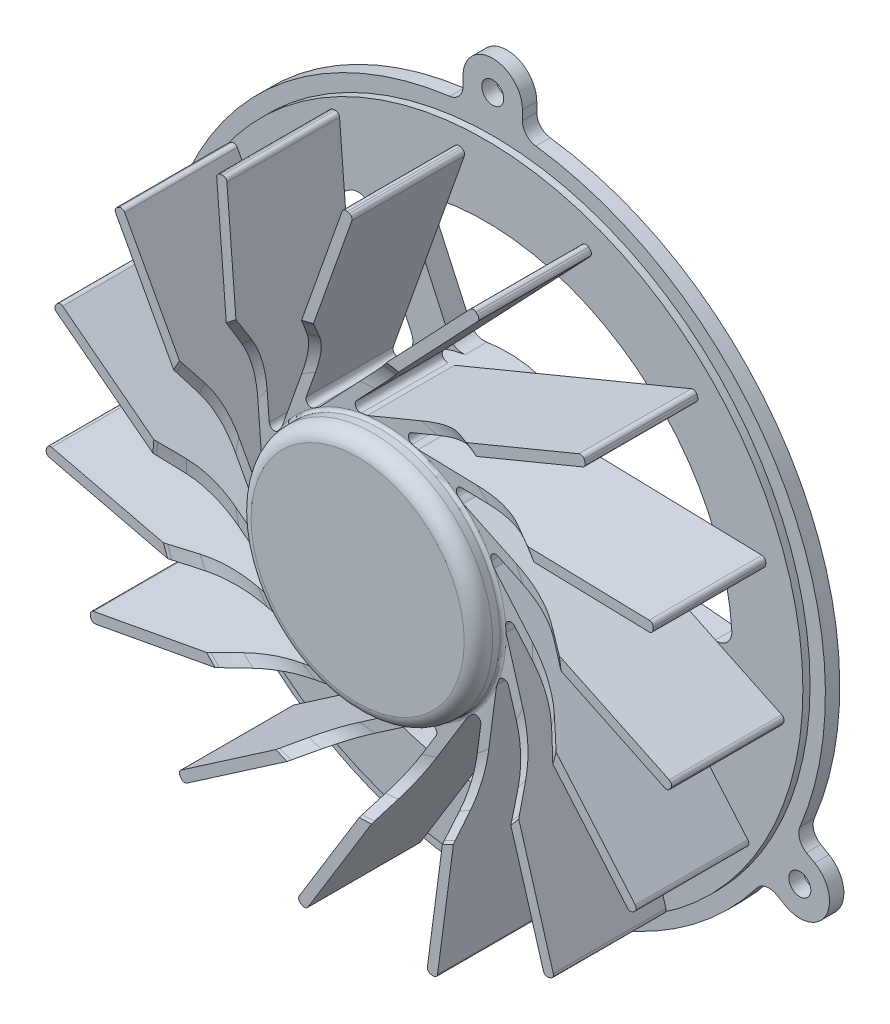
SolidWorks part; units mm, degrees
ref_plane "Front Plane" through (0, 0, 0) normal (0, 0, 1) x (1, 0, 0)
ref_plane "Top Plane" through (0, 0, 0) normal (0, 1, 0) x (1, 0, 0)
ref_plane "Right Plane" through (0, 0, 0) normal (1, 0, 0) x (0, 0, -1)
sketch "Sketch1" plane through (0, 0, 0) normal (0, 0, 1) x (1, 0, 0)
  line L0 (-2.9, 34.641) -> (2.9, 34.641) construction
  line L1 (0, 37.541) -> (0, -32.5) construction
  line L2 (-2.9, 34.641) -> (-2.9, 33.7141)
  line L3 (2.9, 34.641) -> (2.9, 33.7141)
  line L4 (28.55, -19.832) -> (27.7473, -19.3685)
  line L5 (31.45, -14.809) -> (30.6473, -14.3456)
  line L6 (-31.45, -14.809) -> (-30.6473, -14.3456)
  line L7 (-28.55, -19.832) -> (-27.7473, -19.3685)
  line L8 (0, 0) -> (2.9, 32.3704) construction
  line L9 (0, 0) -> (26.5836, -18.6967) construction
  line L10 (0, 0) -> (-29.4836, -13.6737) construction
  line L11 (0, 0) -> (-4.9858, 10.9152) construction
  line L12 (22.4164, -0.1297) -> (13.1694, 0.7526)
  line L13 (-11.0959, 19.478) -> (-7.2365, 11.0288)
  line L14 (12.7895, -3.2293) -> (22.0364, -4.1116)
  line L15 (-3.5981, 12.6907) -> (-7.4575, 21.1399)
  line L17 (-11.3205, -19.3483) -> (-5.933, -11.7813)
  line L18 (-9.1914, -9.4614) -> (-14.579, -17.0283)
  line L19 (0, 0) -> (-6.9599, -9.7754) construction
  line L20 (0, 0) -> (23.991, -2.289) construction
  arc A0 (-4.2059, 32.2267) -> (-30.0121, -12.471) centre (0, 0) ccw
  circle A1 centre (0, 34.641) radius 1.075
  arc A2 (2.9, 34.641) -> (-2.9, 34.641) centre (0, 34.641) ccw
  arc A3 (28.55, -19.832) -> (31.45, -14.809) centre (30, -17.3205) ccw
  circle A4 centre (30, -17.3205) radius 1.075
  arc A5 (-31.45, -14.809) -> (-28.55, -19.832) centre (-30, -17.3205) ccw
  circle A6 centre (-30, -17.3205) radius 1.075
  arc A7 (-25.8062, -19.7558) -> (25.8062, -19.7558) centre (0, 0) ccw
  arc A8 (30.0121, -12.471) -> (4.2059, 32.2267) centre (0, 0) ccw
  arc A9 (-27.7473, -19.3685) -> (-25.8062, -19.7558) centre (-26.9973, -20.6676) cw
  arc A10 (-30.6473, -14.3456) -> (-30.0121, -12.471) centre (-31.3973, -13.0465) ccw
  arc A11 (27.7473, -19.3685) -> (25.8062, -19.7558) centre (26.9973, -20.6676) ccw
  arc A12 (30.6473, -14.3456) -> (30.0121, -12.471) centre (31.3973, -13.0465) cw
  arc A13 (2.9, 33.7141) -> (4.2059, 32.2267) centre (4.4, 33.7141) ccw
  arc A14 (-2.9, 33.7141) -> (-4.2059, 32.2267) centre (-4.4, 33.7141) cw
  arc A15 (-13.2873, 20.1062) -> (-16.8496, -17.2308) centre (0, 0) ccw
  arc A16 (11.8328, 1.9963) -> (-1.9855, 11.8346) centre (0, 0) ccw
  arc A17 (24.0561, 1.454) -> (-6.4975, 23.2076) centre (0, 0) ccw
  arc A18 (-10.7688, -21.5602) -> (23.3471, -5.9768) centre (0, 0) ccw
  arc A19 (-4.1876, -11.2456) -> (11.2418, -4.1978) centre (0, 0) ccw
  arc A20 (-7.6452, 9.2494) -> (-9.2563, -7.6368) centre (0, 0) ccw
  arc A21 (-11.3205, -19.3483) -> (-10.7688, -21.5602) centre (-10.0986, -20.2183) ccw
  arc A22 (-14.579, -17.0283) -> (-16.8496, -17.2308) centre (-15.8009, -16.1583) cw
  arc A23 (-9.1914, -9.4614) -> (-9.2563, -7.6368) centre (-10.4134, -8.5914) ccw
  arc A24 (-5.933, -11.7813) -> (-4.1876, -11.2456) centre (-4.711, -12.6513) cw
  arc A25 (12.7895, -3.2293) -> (11.2418, -4.1978) centre (12.647, -4.7226) ccw
  arc A26 (22.0364, -4.1116) -> (23.3471, -5.9768) centre (21.894, -5.6048) cw
  arc A27 (13.1694, 0.7526) -> (11.8328, 1.9963) centre (13.3119, 2.2458) cw
  arc A28 (-11.0959, 19.478) -> (-13.2873, 20.1062) centre (-12.4603, 18.8548) ccw
  arc A29 (-6.4975, 23.2076) -> (-7.4575, 21.1399) centre (-6.0931, 21.7631) ccw
  arc A30 (-3.5981, 12.6907) -> (-1.9855, 11.8346) centre (-2.2337, 13.3139) ccw
  arc A31 (-7.2365, 11.0288) -> (-7.6452, 9.2494) centre (-8.6009, 10.4055) cw
  arc A32 (24.0561, 1.454) -> (22.4164, -0.1297) centre (22.5588, 1.3635) cw
  circle A33 centre (0, 0) radius 31
  point P32 (26.5836, -18.6967)
  point P37 (2.9, 32.3704)
  point P60 (0, 0)
  point P78 (-6.7353, 9.9316)
  dimension "D1" = 65
  dimension "D2" = 2.15
  dimension "D3" = 5.8
  dimension "D6" = 1.5
  dimension "D7" = 8.4
  dimension "D8" = 24
  dimension "D12" = 1.5
  dimension "D13" = 1.5
  dimension "D14" = 62
  dimension "D5" = 120
  dimension "D9" = 2
  dimension "D10" = 2
  dimension "D15" = 60
  dimension "D4" = 3
  dimension "D11" = 3
extrude "extrude-bottom" add sketch "Sketch1" along normal blind 1.4 contours A33 A17 A32 L12 A27 A16 A30 L15 A29 L14 A26 A18 A21 L17 A24 A19 A25 L13 A31 A20 A23 L18 A22 A15 A28 | L2 A14 A0 A10 L6 A5 L7 A9 A7 A11 L4 A3 L5 A12 A8 A13 L3 A2 A33 A6 A4 A1 region at (0, 36.58, 0) region at (0, 0, 0)
extrude "extrude-offset" add sketch "Sketch1<3>" along normal blind 2.1 contours A33 A17 A32 L12 A27 A16 A30 L15 A29 L14 A26 A18 A21 L17 A24 A19 A25 L13 A31 A20 A23 L18 A22 A15 A28 region at (0, 0, 0)
sketch "Sketch1<3>" plane through (0, 0, 0) normal (0, 0, 1) x (1, 0, 0) same geometry as "Sketch1"
sketch "Sketch2" plane through (0, 0, 2.1) normal (0, 0, 1) x (1, 0, 0)
  circle A0 centre (0, 0) radius 12
extrude "extrude-fan-base" add sketch "Sketch2" along normal blind 1.5
sketch "Sketch3" plane through (0, 0, 3.6) normal (0, 0, 1) x (1, 0, 0)
  line L0 (0, 41.7552) -> (0, -41.8706) construction
  line L1 (56.9418, 0) -> (-60.0855, 0) construction
  line L2 (0, 12) -> (63.232, 12) construction
  line L3 (63.232, 12) -> (-76.4509, 12) construction
  line L4 (0, 12) -> (22.1731, 21.1844) construction
  line L5 (21.6122, 21.4933) -> (-1.5489, 11.8996)
  line L6 (2.7699, 12.6061) -> (21.9949, 20.5694)
  line L7 (22.1348, 21.2768) -> (22.2114, 21.092)
  line L8 (28.4858, 10.8446) -> (3.425, 11.5008)
  line L9 (7.6578, 10.3897) -> (28.4597, 9.8449)
  line L10 (28.8752, 10.4343) -> (28.87, 10.2343)
  line L11 (4.8808, 10.9625) -> (28.8726, 10.3343) construction
  line L12 (30.434, -1.6792) -> (7.8067, 9.1135)
  line L13 (11.2216, 6.3767) -> (30.0035, -2.5818)
  line L14 (30.6228, -2.2124) -> (30.5367, -2.393)
  line L15 (8.9177, 8.0296) -> (30.5798, -2.3027) construction
  line L16 (27.1199, -13.9127) -> (10.8386, 5.1503)
  line L17 (12.8451, 1.2612) -> (26.3594, -14.5621)
  line L18 (27.0755, -14.4766) -> (26.9234, -14.6065)
  line L19 (11.4127, 3.7082) -> (26.9994, -14.5415) construction
  line L20 (19.1164, -23.7405) -> (11.9963, 0.2966)
  line L21 (12.2475, -4.0724) -> (18.1576, -24.0245)
  line L22 (18.8465, -24.2376) -> (18.6547, -24.2944)
  line L23 (11.9343, -1.2543) -> (18.7506, -24.266) construction
  line L24 (7.8076, -29.4634) -> (11.0798, -4.6084)
  line L25 (9.5323, -8.7018) -> (6.8162, -29.3328)
  line L26 (7.3588, -29.8077) -> (7.1605, -29.7816)
  line L27 (10.3923, -6) -> (7.2597, -29.7947) construction
  line L28 (-4.8512, -30.0918) -> (8.2475, -8.7166)
  line L29 (5.1688, -11.8267) -> (-5.7039, -29.5693)
  line L30 (-5.4013, -30.2238) -> (-5.5718, -30.1193)
  line L31 (7.0534, -9.7082) -> (-5.4865, -30.1716) construction
  line L32 (-16.6712, -25.517) -> (3.9891, -11.3175)
  line L33 (-0.0884, -12.9065) -> (-17.2376, -24.6929)
  line L34 (-17.2274, -25.4139) -> (-17.3407, -25.2491)
  line L35 (2.4949, -11.7378) -> (-17.2841, -25.3315) construction
  line L36 (-25.6086, -16.5302) -> (-0.959, -11.9616)
  line L37 (-5.3303, -11.7548) -> (-25.7909, -15.5469)
  line L38 (-26.0748, -16.2097) -> (-26.1113, -16.0131)
  line L39 (-2.4949, -11.7378) -> (-26.0931, -16.1114) construction
  line L40 (-30.1181, -4.6851) -> (-5.7413, -10.5374)
  line L41 (-9.6506, -8.5705) -> (-29.8846, -3.7127)
  line L42 (-30.4136, -4.2028) -> (-30.367, -4.0083)
  line L43 (-7.0534, -9.7082) -> (-30.3903, -4.1055) construction
  line L44 (-29.4198, 7.9701) -> (-9.5309, -7.2912)
  line L45 (-12.3022, -3.9043) -> (-28.8111, 8.7634)
  line L46 (-29.4937, 8.5309) -> (-29.3719, 8.6896)
  line L47 (-10.3923, -6) -> (-29.4328, 8.6103) construction
  line L48 (-23.6346, 19.2472) -> (-11.6725, -2.7843)
  line L49 (-12.8266, 1.437) -> (-22.7558, 19.7243)
  line L50 (-23.474, 19.7896) -> (-23.2982, 19.885)
  line L51 (-11.9343, -1.2543) -> (-23.3861, 19.8373) construction
  line L52 (-13.7628, 27.1962) -> (-11.7958, 2.2041)
  line L53 (-11.1332, 6.5298) -> (-12.7659, 27.2747)
  line L54 (-13.3954, 27.6264) -> (-13.196, 27.6421)
  line L55 (-11.4127, 3.7082) -> (-13.2957, 27.6342) construction
  line L56 (-1.5112, 30.4428) -> (-9.8796, 6.8113)
  line L57 (-7.5148, 10.4936) -> (-0.5686, 30.109)
  line L58 (-1.0006, 30.6863) -> (-0.8121, 30.6196)
  line L59 (-8.9177, 8.0296) -> (-0.9064, 30.653) construction
  line L60 (11.0016, 28.4256) -> (-6.255, 10.2408)
  line L61 (-2.597, 12.6429) -> (11.727, 27.7372)
  line L62 (11.5671, 28.4404) -> (11.7122, 28.3027)
  line L63 (-4.8808, 10.9625) -> (11.6397, 28.3715) construction
  circle A0 centre (0, 0) radius 30 construction
  arc A1 (-1.5489, 11.8996) -> (-2.1449, 11.8068) centre (0, 0) ccw
  circle A2 centre (0, 0) radius 12 construction
  arc A3 (21.9949, 20.5694) -> (22.2114, 21.092) centre (21.8418, 20.9389) ccw
  arc A4 (21.6122, 21.4933) -> (22.1348, 21.2768) centre (21.7653, 21.1237) cw
  arc A5 (2.7699, 12.6061) -> (2.8428, 11.6584) centre (2.9612, 12.1442) ccw
  arc A6 (7.6578, 10.3897) -> (7.3389, 9.4942) centre (7.6447, 9.8898) ccw
  arc A7 (28.4858, 10.8446) -> (28.8752, 10.4343) centre (28.4754, 10.4447) cw
  arc A8 (28.4597, 9.8449) -> (28.87, 10.2343) centre (28.4701, 10.2448) ccw
  arc A9 (11.2216, 6.3767) -> (10.5661, 5.6884) centre (11.0063, 5.9254) ccw
  arc A10 (30.434, -1.6792) -> (30.6228, -2.2124) centre (30.2618, -2.0402) cw
  arc A11 (30.0035, -2.5818) -> (30.5367, -2.393) centre (30.1757, -2.2208) ccw
  arc A12 (12.8451, 1.2612) -> (11.9663, 0.899) centre (12.4649, 0.9365) ccw
  arc A13 (27.1199, -13.9127) -> (27.0755, -14.4766) centre (26.8157, -14.1724) cw
  arc A14 (26.3594, -14.5621) -> (26.9234, -14.6065) centre (26.6636, -14.3023) ccw
  arc A15 (12.2475, -4.0724) -> (11.2974, -4.0458) centre (11.7681, -4.2144) ccw
  arc A16 (19.1164, -23.7405) -> (18.8465, -24.2376) centre (18.7329, -23.8541) cw
  arc A17 (18.1576, -24.0245) -> (18.6547, -24.2944) centre (18.5411, -23.9109) ccw
  arc A18 (9.5323, -8.7018) -> (8.6751, -8.2911) centre (9.0366, -8.6366) ccw
  arc A19 (7.8076, -29.4634) -> (7.3588, -29.8077) centre (7.411, -29.4112) cw
  arc A20 (6.8162, -29.3328) -> (7.1605, -29.7816) centre (7.2127, -29.385) ccw
  arc A21 (5.1688, -11.8267) -> (4.5528, -11.1028) centre (4.7425, -11.5654) ccw
  arc A22 (-4.8512, -30.0918) -> (-5.4013, -30.2238) centre (-5.1923, -29.8828) cw
  arc A23 (-5.7039, -29.5693) -> (-5.5718, -30.1193) centre (-5.3628, -29.7783) ccw
  arc A24 (-0.0884, -12.9065) -> (-0.3567, -11.9947) centre (-0.3716, -12.4945) ccw
  arc A25 (-16.6712, -25.517) -> (-17.2274, -25.4139) centre (-16.8978, -25.1874) cw
  arc A26 (-17.2376, -24.6929) -> (-17.3407, -25.2491) centre (-17.0111, -25.0225) ccw
  arc A27 (-5.3303, -11.7548) -> (-5.2046, -10.8126) centre (-5.4214, -11.2631) ccw
  arc A28 (-25.6086, -16.5302) -> (-26.0748, -16.2097) centre (-25.6815, -16.1369) cw
  arc A29 (-25.7909, -15.5469) -> (-26.1113, -16.0131) centre (-25.718, -15.9402) ccw
  arc A30 (-9.6506, -8.5705) -> (-9.1525, -7.7609) centre (-9.5338, -8.0843) ccw
  arc A31 (-30.1181, -4.6851) -> (-30.4136, -4.2028) centre (-30.0247, -4.2961) cw
  arc A32 (-29.8846, -3.7127) -> (-30.367, -4.0083) centre (-29.978, -4.1017) ccw
  arc A33 (-12.3022, -3.9043) -> (-11.5179, -3.3673) centre (-11.9978, -3.5076) ccw
  arc A34 (-29.4198, 7.9701) -> (-29.4937, 8.5309) centre (-29.1763, 8.2874) cw
  arc A35 (-28.8111, 8.7634) -> (-29.3719, 8.6896) centre (-29.0546, 8.4461) ccw
  arc A36 (-12.8266, 1.437) -> (-11.8917, 1.6086) centre (-12.3872, 1.6756) ccw
  arc A37 (-23.6346, 19.2472) -> (-23.474, 19.7896) centre (-23.2831, 19.438) cw
  arc A38 (-22.7558, 19.7243) -> (-23.2982, 19.885) centre (-23.1073, 19.5335) ccw
  arc A39 (-11.1332, 6.5298) -> (-10.2093, 6.3063) centre (-10.6347, 6.569) ccw
  arc A40 (-13.7628, 27.1962) -> (-13.3954, 27.6264) centre (-13.364, 27.2276) cw
  arc A41 (-12.7659, 27.2747) -> (-13.196, 27.6421) centre (-13.1646, 27.2433) ccw
  arc A42 (-7.5148, 10.4936) -> (-6.7617, 9.9136) centre (-7.0434, 10.3267) ccw
  arc A43 (-1.5112, 30.4428) -> (-1.0006, 30.6863) centre (-1.1342, 30.3093) cw
  arc A44 (-0.5686, 30.109) -> (-0.8121, 30.6196) centre (-0.9456, 30.2425) ccw
  arc A45 (-2.597, 12.6429) -> (-2.1449, 11.8068) centre (-2.2343, 12.2987) ccw
  arc A46 (11.0016, 28.4256) -> (11.5671, 28.4404) centre (11.2918, 28.1502) cw
  arc A47 (11.727, 27.7372) -> (11.7122, 28.3027) centre (11.4369, 28.0125) ccw
  arc A48 (-11.6725, -2.7843) -> (-11.5179, -3.3673) centre (0, 0) ccw
  arc A49 (-9.5309, -7.2912) -> (-9.1525, -7.7609) centre (0, 0) ccw
  arc A50 (-5.7413, -10.5374) -> (-5.2046, -10.8126) centre (0, 0) ccw
  arc A51 (-0.959, -11.9616) -> (-0.3567, -11.9947) centre (0, 0) ccw
  arc A52 (3.9891, -11.3175) -> (4.5528, -11.1028) centre (0, 0) ccw
  arc A53 (8.2475, -8.7166) -> (8.6751, -8.2911) centre (0, 0) ccw
  arc A54 (11.0798, -4.6084) -> (11.2974, -4.0458) centre (0, 0) ccw
  arc A55 (11.9963, 0.2966) -> (11.9663, 0.899) centre (0, 0) ccw
  arc A56 (10.8386, 5.1503) -> (10.5661, 5.6884) centre (0, 0) ccw
  arc A57 (7.8067, 9.1135) -> (7.3389, 9.4942) centre (0, 0) ccw
  arc A58 (3.425, 11.5008) -> (2.8428, 11.6584) centre (0, 0) ccw
  arc A59 (-6.255, 10.2408) -> (-6.7617, 9.9136) centre (0, 0) ccw
  arc A60 (-9.8796, 6.8113) -> (-10.2093, 6.3063) centre (0, 0) ccw
  arc A61 (-11.7958, 2.2041) -> (-11.8917, 1.6086) centre (0, 0) ccw
  point P194 (0, 0)
  dimension "D1" = 60
  dimension "D4" = 0.4
  dimension "D5" = 0.5
  dimension "D2" = 1
  dimension "D3" = 24
  dimension "D6" = 15
extrude "Boss-Extrude4" add sketch "Sketch3" along normal blind 11
sketch "Sketch4" plane through (0, 0, 0) normal (0, 1, 0) x (1, 0, 0)
  line L0 (-30.4136, -3.6) -> (-30.4247, -14.6) construction
  line L1 (-30.4247, -14.6) -> (-30.4192, -9.1) construction
  line L2 (-30.4192, -9.1) -> (30.6618, -9.1) construction
  line L3 (30.6618, -14.6) -> (30.6618, -3.6) construction
  line L4 (30.6618, -9.1) -> (30.6228, -14.6) construction
  line L5 (30.6228, -14.6) -> (-10, -14.6) construction
  line L6 (-20, -14.6) -> (-20, -15.6)
  line L7 (-19.7759, -14.4457) -> (-18.1011, -13.2361)
  line L8 (0, 0) -> (0, -14.6) construction
  line L9 (-14.588, -12.1) -> (-12.0053, -12.1)
  line L10 (-11.7053, -12.4) -> (-11.7053, -13.1141)
  line L11 (-20, -15.6) -> (-10, -15.6)
  line L13 (0, -14.6) -> (-30, -14.6) construction
  line L14 (-10, -15.6) -> (-10, -14.6)
  arc A0 (-11.7053, -13.1141) -> (-10, -14.6) centre (-10.2053, -13.1141) ccw
  arc A1 (-20, -14.6) -> (-19.7759, -14.4457) centre (-23.289, -9.5818) ccw
  arc A2 (-18.1011, -13.2361) -> (-14.588, -12.1) centre (-14.588, -18.1) cw
  arc A3 (-12.0053, -12.1) -> (-11.7053, -12.4) centre (-12.0053, -12.4) cw
  point P19 (-15.3971, -14.6)
  point P25 (-16.5282, -12.1)
  point P28 (-11.7053, -12.1)
  dimension "D5" = 1.5
  dimension "D6" = 6
  dimension "D7" = 0.3
  dimension "D1" = 10
  dimension "D2" = 2.5
  dimension "D3" = 30
  dimension "D8" = 10
  dimension "D9" = 1
revolve "Cut-Revolve5" cut sketch "Sketch4" angle 360 about L8
